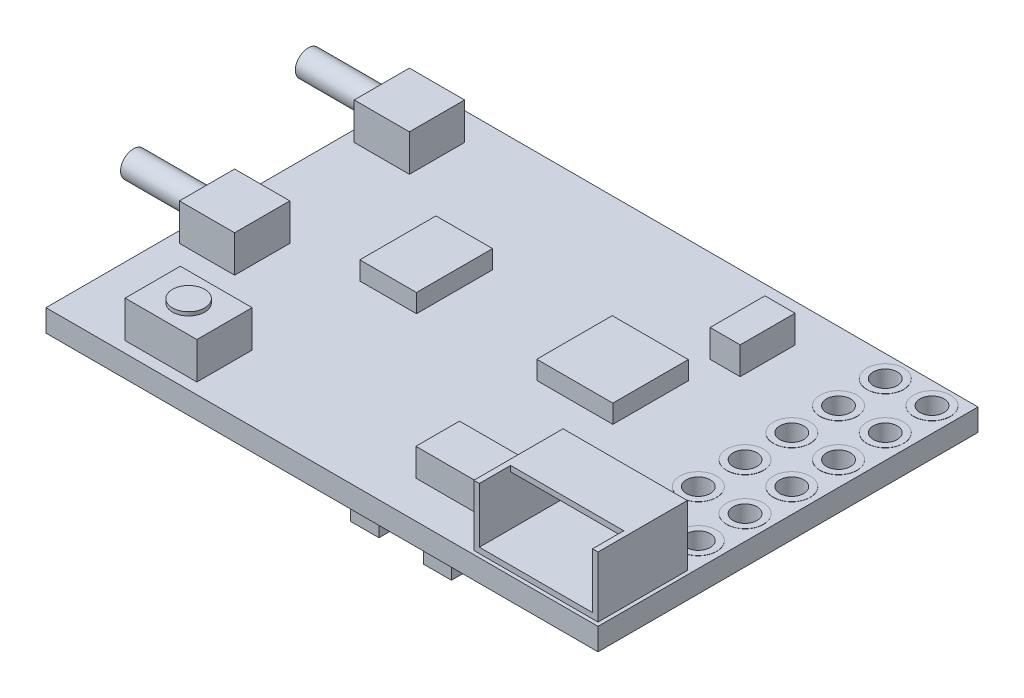
SolidWorks part; units mm, degrees
ref_plane "Front Plane" through (0, 0, 0) normal (0, 0, 1) x (1, 0, 0)
ref_plane "Top Plane" through (0, 0, 0) normal (0, 1, 0) x (1, 0, 0)
ref_plane "Right Plane" through (0, 0, 0) normal (1, 0, 0) x (0, 0, -1)
sketch "Sketch1" plane through (0, 0, 0) normal (0, 1, 0) x (1, 0, 0)
  line L1 (-15, 10.325) -> (15, 10.325)
  line L2 (-15, 10.325) -> (-15, -10.325)
  line L3 (-15, -10.325) -> (15, -10.325)
  line L4 (15, 10.325) -> (15, -10.325)
  line L5 (-15, 10.325) -> (15, -10.325) construction
  line L6 (-15, -10.325) -> (15, 10.325) construction
  point P0 (0, 0)
  dimension "D1" = 30
  dimension "D2" = 20.65
extrude "Boss-Extrude1" add sketch "Sketch1" along normal blind 1.2
sketch "Sketch2" plane through (0, 1.2, 0) normal (0, 1, 0) x (1, 0, 0)
  line L0 (13.7, 10.325) -> (13.7, -10.325) construction
  line L1 (15, 10.325) -> (-15, 10.325) construction
  line L2 (-15, -10.325) -> (15, -10.325) construction
  line L3 (11.16, 9.125) -> (13.7, 9.125) construction
  line L4 (15, -10.325) -> (15, 10.325) construction
  line L5 (13.7, 9.125) -> (13.7, 6.585) construction
  circle A0 centre (13.7, 9.125) radius 0.65
  circle A1 centre (11.16, 9.125) radius 0.65
  circle A2 centre (11.16, 6.585) radius 0.65
  circle A3 centre (11.16, 4.045) radius 0.65
  circle A4 centre (11.16, 1.505) radius 0.65
  circle A5 centre (11.16, -1.035) radius 0.65
  circle A6 centre (11.16, -3.575) radius 0.65
  circle A7 centre (13.7, 6.585) radius 0.65
  circle A8 centre (13.7, 4.045) radius 0.65
  circle A9 centre (13.7, 1.505) radius 0.65
  circle A10 centre (13.7, -1.035) radius 0.65
  circle A11 centre (13.7, -3.575) radius 0.65
  dimension "D3" = 1.3
  dimension "D1" = 1.3
  dimension "D2" = 2
  dimension "D4" = 1.2
  dimension "D6" = 2.54
  dimension "D5" = 6
extrude "Cut-Extrude1" cut sketch "Sketch2" against normal up to next
sketch "Sketch3" plane through (0, 1.2, 0) normal (0, 1, 0) x (1, 0, 0)
  line L0 (-15, -10.325) -> (15, -10.325) construction
  line L1 (14.8, -10.125) -> (8.05, -10.125)
  line L2 (14.8, -10.125) -> (14.8, -5.275)
  line L3 (14.8, -5.275) -> (8.05, -5.275)
  line L4 (8.05, -10.125) -> (8.05, -5.275)
  line L5 (15, -10.325) -> (15, 10.325) construction
  dimension "D1" = 6.75
  dimension "D2" = 4.85
  dimension "D3" = 0.2
  dimension "D4" = 0.2
extrude "Boss-Extrude2" add sketch "Sketch3" along normal blind 3.3
sketch "Sketch4" plane through (0, 1.2, 0) normal (0, 1, 0) x (1, 0, 0)
  line L1 (-14.4, 8.825) -> (-11.4, 8.825)
  line L2 (-14.4, 8.825) -> (-14.4, 5.825)
  line L3 (-14.4, 5.825) -> (-11.4, 5.825)
  line L4 (-11.4, 8.825) -> (-11.4, 5.825)
  line L5 (-15, 10.325) -> (-15, -10.325) construction
  line L6 (-15, 2.575) -> (15, 2.575) construction
  line L7 (15, -10.325) -> (15, 10.325) construction
  line L8 (-14.4, -0.675) -> (-11.4, -0.675)
  line L9 (-11.4, -3.675) -> (-11.4, -0.675)
  line L10 (-14.4, -3.675) -> (-11.4, -3.675)
  line L11 (-14.4, -3.675) -> (-14.4, -0.675)
  line L12 (-14.4, -2.175) -> (-11.4, -2.175) construction
  line L13 (-14.4, 7.325) -> (-11.4, 7.325) construction
  line L14 (15, 10.325) -> (-15, 10.325) construction
  dimension "D1" = 3
  dimension "D2" = 3
  dimension "D3" = 3
  dimension "D4" = 0.6
  dimension "D5" = 9.5
extrude "Boss-Extrude3" add sketch "Sketch4" along normal blind 2
sketch "Sketch5" plane through (0, 1.2, 0) normal (0, 1, 0) x (1, 0, 0)
  line L0 (-15, 10.325) -> (-15, -10.325) construction
  line L1 (-11.3, -9.725) -> (-7.4, -9.725)
  line L2 (-11.3, -9.725) -> (-11.3, -6.725)
  line L3 (-11.3, -6.725) -> (-7.4, -6.725)
  line L4 (-7.4, -9.725) -> (-7.4, -6.725)
  line L5 (-15, -10.325) -> (15, -10.325) construction
  dimension "D1" = 3.9
  dimension "D2" = 3
  dimension "D3" = 3.7
  dimension "D4" = 0.6
extrude "Boss-Extrude4" add sketch "Sketch5" along normal blind 2
sketch "Sketch6" plane through (0, 3.2, 0) normal (0, 1, 0) x (1, 0, 0)
  line L0 (-11.3, -8.225) -> (-7.4, -8.225) construction
  line L1 (-11.3, -6.725) -> (-11.3, -9.725) construction
  line L2 (-7.4, -9.725) -> (-7.4, -6.725) construction
  line L3 (-9.35, -6.725) -> (-9.35, -9.725) construction
  line L4 (-7.4, -6.725) -> (-11.3, -6.725) construction
  line L5 (-11.3, -9.725) -> (-7.4, -9.725) construction
  circle A0 centre (-9.35, -8.225) radius 0.875
  dimension "D1" = 1.75
extrude "Boss-Extrude5" add sketch "Sketch6" along normal blind 0.2
sketch "Sketch7" plane through (0, 4.5, 0) normal (0, 1, 0) x (1, 0, 0)
  line L0 (11.425, -5.275) -> (11.425, -10.125) construction
  line L1 (14.8, -5.275) -> (8.05, -5.275) construction
  line L2 (8.05, -10.125) -> (14.8, -10.125) construction
  line L3 (8.05, -10.125) -> (14.8, -10.125) construction
  line L4 (8.35, -10.125) -> (14.5, -10.125)
  line L5 (8.35, -10.125) -> (8.35, -8.425)
  line L6 (8.35, -8.425) -> (14.5, -8.425)
  line L7 (14.5, -10.125) -> (14.5, -8.425)
  line L8 (8.05, -5.275) -> (8.05, -10.125) construction
  point P12 (11.425, -8.425)
  dimension "D1" = 0.3
  dimension "D2" = 1.7
extrude "Cut-Extrude2" cut sketch "Sketch7" against normal offset from surface (3 mm away) 0.3 up to face at (11.16, 1.2, 4.225)
sketch "Sketch8" plane through (0, 0, 8.425) normal (0, 0, 1) x (1, 0, 0)
  line L0 (14.5, 1.5) -> (14.5, 4.5) construction
  line L1 (8.35, 1.5) -> (14.5, 1.5)
  line L2 (8.35, 1.5) -> (8.35, 4.2)
  line L3 (8.35, 4.2) -> (14.5, 4.2)
  line L4 (14.5, 1.5) -> (14.5, 4.2)
  line L5 (14.5, 4.5) -> (8.35, 4.5) construction
  dimension "D1" = 0.3
extrude "Cut-Extrude3" cut sketch "Sketch8" against normal offset from surface (2.85 mm away) 0.3 up to face at (11.425, 2.85, 5.275)
sketch "Sketch9" plane through (0, 1.2, 0) normal (0, 1, 0) x (1, 0, 0)
  line L1 (5.896, 3.685) -> (1.7624, 3.685)
  line L2 (5.896, 3.685) -> (5.896, -0.4166)
  line L3 (5.896, -0.4166) -> (1.7624, -0.4166)
  line L4 (1.7624, 3.685) -> (1.7624, -0.4166)
  line L5 (-7.7224, 3.5888) -> (-4.6463, 3.5888)
  line L6 (-7.7224, 3.5888) -> (-7.7224, -0.5447)
  line L7 (-7.7224, -0.5447) -> (-4.6463, -0.5447)
  line L8 (-4.6463, 3.5888) -> (-4.6463, -0.5447)
extrude "Boss-Extrude6" add sketch "Sketch9" along normal blind 1
sketch "Sketch10" plane through (0, 1.2, 0) normal (0, 1, 0) x (1, 0, 0)
  line L1 (7.1136, 8.2672) -> (5.4794, 8.2672)
  line L2 (7.1136, 8.2672) -> (7.1136, 5.2871)
  line L3 (7.1136, 5.2871) -> (5.4794, 5.2871)
  line L4 (5.4794, 8.2672) -> (5.4794, 5.2871)
  line L5 (7.5302, -5.928) -> (3.0762, -5.928)
  line L6 (7.5302, -5.928) -> (7.5302, -8.2992)
  line L7 (7.5302, -8.2992) -> (3.0762, -8.2992)
  line L8 (3.0762, -5.928) -> (3.0762, -8.2992)
extrude "Boss-Extrude7" add sketch "Sketch10" along normal blind 1.5
sketch "Sketch11" plane through (0, 0, 0) normal (0, -1, 0) x (1, 0, 0)
  line L1 (-6.3538, 2.621) -> (0.4959, 2.621)
  line L2 (-6.3538, 2.621) -> (-6.3538, -4.2287)
  line L3 (-6.3538, -4.2287) -> (0.4959, -4.2287)
  line L4 (0.4959, 2.621) -> (0.4959, -4.2287)
  line L6 (-15, -10.325) -> (-15, 10.325) construction
  line L7 (6.1467, 9.4396) -> (4.628, 9.4396)
  line L8 (6.1467, 9.4396) -> (6.1467, 6.4332)
  line L9 (6.1467, 6.4332) -> (4.628, 6.4332)
  line L10 (4.628, 9.4396) -> (4.628, 6.4332)
  line L11 (2.1795, 9.4086) -> (0.6298, 9.4086)
  line L12 (2.1795, 9.4086) -> (2.1795, 6.3402)
  line L13 (2.1795, 6.3402) -> (0.6298, 6.3402)
  line L14 (0.6298, 9.4086) -> (0.6298, 6.3402)
  line L15 (4.9689, 5.6274) -> (6.1467, 5.6274)
  line L16 (4.9689, 5.6274) -> (4.9689, 2.8689)
  line L17 (4.9689, 2.8689) -> (6.1467, 2.8689)
  line L18 (6.1467, 5.6274) -> (6.1467, 2.8689)
  line L19 (-15, -4.3837) -> (-12.1398, -4.3837)
  line L20 (-15, -4.3837) -> (-15, -8.5679)
  line L21 (-15, -8.5679) -> (-12.1398, -8.5679)
  line L22 (-12.1398, -4.3837) -> (-12.1398, -8.5679)
  line L23 (-13.5965, 3.7987) -> (-11.21, 3.7987)
  line L24 (-13.5965, 3.7987) -> (-13.5965, 0.6993)
  line L25 (-13.5965, 0.6993) -> (-11.21, 0.6993)
  line L26 (-11.21, 3.7987) -> (-11.21, 0.6993)
  line L27 (-10.0012, -6.3053) -> (-8.7304, -6.3053)
  line L28 (-10.0012, -6.3053) -> (-10.0012, -9.4667)
  line L29 (-10.0012, -9.4667) -> (-8.7304, -9.4667)
  line L30 (-8.7304, -6.3053) -> (-8.7304, -9.4667)
extrude "Boss-Extrude8" add sketch "Sketch11" along normal blind 1.5
sketch "Sketch12" plane through (0, 1.2, 0) normal (0, 1, 0) x (1, 0, 0)
  circle A0 centre (11.16, 9.125) radius 1
  circle A1 centre (13.7, 9.125) radius 1
  circle A2 centre (13.7, 6.585) radius 1
  circle A3 centre (11.16, 6.585) radius 1
  circle A4 centre (11.16, 4.045) radius 1
  circle A5 centre (13.7, 4.045) radius 1
  circle A6 centre (13.7, 1.505) radius 1
  circle A7 centre (11.16, 1.505) radius 1
  circle A8 centre (11.16, -1.035) radius 1
  circle A9 centre (11.16, -3.575) radius 1
  circle A10 centre (13.7, -3.575) radius 1
  circle A11 centre (13.7, -1.035) radius 1
  circle A12 centre (11.16, -3.575) radius 0.65 construction
  circle A13 centre (13.7, -3.575) radius 0.65 construction
  circle A14 centre (13.7, -1.035) radius 0.65 construction
  circle A15 centre (11.16, -1.035) radius 0.65 construction
  circle A16 centre (11.16, 1.505) radius 0.65 construction
  circle A17 centre (13.7, 1.505) radius 0.65 construction
  circle A18 centre (13.7, 4.045) radius 0.65 construction
  circle A19 centre (11.16, 4.045) radius 0.65 construction
  circle A20 centre (11.16, 6.585) radius 0.65 construction
  circle A21 centre (13.7, 6.585) radius 0.65 construction
  circle A22 centre (13.7, 9.125) radius 0.65 construction
  circle A23 centre (11.16, 9.125) radius 0.65 construction
  circle A24 centre (11.16, -3.575) radius 0.65
  circle A25 centre (13.7, -3.575) radius 0.65
  circle A26 centre (13.7, -1.035) radius 0.65
  circle A27 centre (11.16, -1.035) radius 0.65
  circle A28 centre (11.16, 1.505) radius 0.65
  circle A29 centre (13.7, 1.505) radius 0.65
  circle A30 centre (13.7, 4.045) radius 0.65
  circle A31 centre (11.16, 4.045) radius 0.65
  circle A32 centre (11.16, 6.585) radius 0.65
  circle A33 centre (13.7, 6.585) radius 0.65
  circle A34 centre (13.7, 9.125) radius 0.65
  circle A35 centre (11.16, 9.125) radius 0.65
  dimension "D1" = 2
extrude "Boss-Extrude9" add sketch "Sketch12" along normal blind 0.01
ref_plane "Plane1" through (0, 0.6, 0) normal (0, 1, 0) x (1, 0, 0)
mirror "Mirror1" about plane through (0, 0.6, 0) normal (0, 1, 0) of "Boss-Extrude9"
sketch "Sketch13" plane through (-14.4, 0, 0) normal (-1, 0, 0) x (0, 0, 1)
  line L0 (-8.825, 1.2) -> (-5.825, 3.2) construction
  line L1 (0.675, 1.2) -> (3.675, 3.2) construction
  circle A0 centre (-7.325, 2.2) radius 0.7
  circle A1 centre (2.175, 2.2) radius 0.7
  dimension "D1" = 1.4
extrude "Boss-Extrude10" add sketch "Sketch13" along normal blind 4
